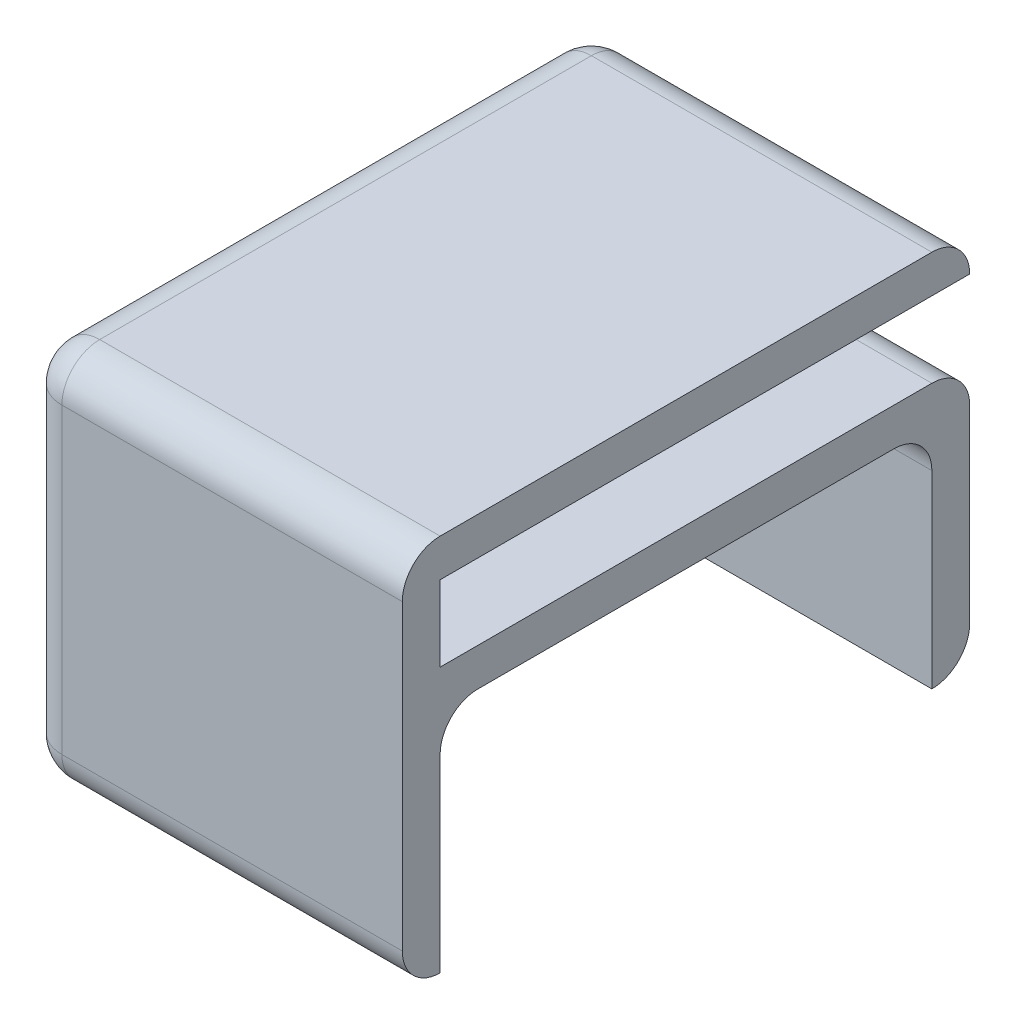
SolidWorks part; units mm, degrees
ref_plane "Front Plane" through (0, 0, 0) normal (0, 0, 1) x (1, 0, 0)
ref_plane "Top Plane" through (0, 0, 0) normal (0, 1, 0) x (1, 0, 0)
ref_plane "Right Plane" through (0, 0, 0) normal (1, 0, 0) x (0, 0, -1)
sketch "Sketch1" plane through (0, 0, 0) normal (0, 1, 0) x (1, 0, 0)
  line L1 (0, 0) -> (10, 0)
  line L2 (0, 0) -> (0, 15)
  line L3 (0, 15) -> (10, 15)
  line L4 (10, 0) -> (10, 15)
  dimension "D1" = 10
  dimension "D2" = 15
extrude "Boss-Extrude1" add sketch "Sketch1" along normal blind 10
shell "Shell1" thickness 1 removed face at (10, 5, -7.5)
sketch "Sketch5" plane through (0, 0, -14) normal (0, 0, 1) x (1, 0, 0)
  line L6 (1, 9) -> (1, 1) construction
  line L7 (1, 7) -> (10, 7)
  line L8 (1, 7) -> (1, 6)
  line L9 (1, 6) -> (10, 6)
  line L10 (10, 7) -> (10, 6)
  line L11 (10, 9) -> (10, 1) construction
  dimension "D1" = 2
  dimension "D2" = 1
extrude "Boss-Extrude4" add sketch "Sketch5" along normal up to next
sketch "Sketch3" plane through (0, 9, 0) normal (0, -1, 0) x (-1, 0, 0)
  circle A0 centre (-7.5, 2.5) radius 0.5
  dimension "D1" = 1
  dimension "D2" = 7.5
  dimension "D3" = 2.5
extrude "Boss-Extrude3" add sketch "Sketch3" along normal blind 0.5
sketch "Sketch6" plane through (0, 7, 0) normal (0, 1, 0) x (1, 0, 0)
  circle A0 centre (7.5, 2.5) radius 0.5
  dimension "D3" = 1
  dimension "D1" = 7.5
  dimension "D2" = 2.5
extrude "Boss-Extrude5" add sketch "Sketch6" along normal blind 0.5
sketch "Sketch8" plane through (0, 1, 0) normal (0, 1, 0) x (1, 0, 0)
  line L1 (1, 14) -> (10, 14)
  line L2 (1, 14) -> (1, 1)
  line L3 (1, 1) -> (10, 1)
  line L4 (10, 14) -> (10, 1)
extrude "Cut-Extrude1" cut sketch "Sketch8" against normal through all
sketch "Sketch10" plane through (10, 0, 0) normal (1, 0, 0) x (0, 0, -1)
  line L0 (15, 10) -> (15, 0) construction
  line L1 (14, 9) -> (15, 9)
  line L2 (14, 9) -> (14, 7)
  line L3 (14, 7) -> (15, 7)
  line L4 (15, 9) -> (15, 7)
  line L5 (1, 7) -> (14, 7) construction
extrude "Cut-Extrude4" cut sketch "Sketch10" against normal up to surface (9 mm away) up to face at (1, 8, -7.5)
fillet "Fillet1" radius 1 2 edges at (0, 0, -7.5) (0, 10, -7.5)
fillet "Fillet2" radius 1 5 edges at (5.5, 0, 0) (0.2929, 0.2929, 0) (0, 5, 0) (0.2929, 9.7071, 0) (5.5, 10, 0)
fillet "Fillet3" radius 1 5 edges at (5.5, 0, -15) (0.2929, 0.2929, -15) (0, 5, -15) (0.2929, 9.7071, -15) (5.5, 10, -15)
fillet "Fillet5" radius 1 3 edges at (5.5, 7, -15) (5.5, 6, -14) (5.5, 6, -1)
